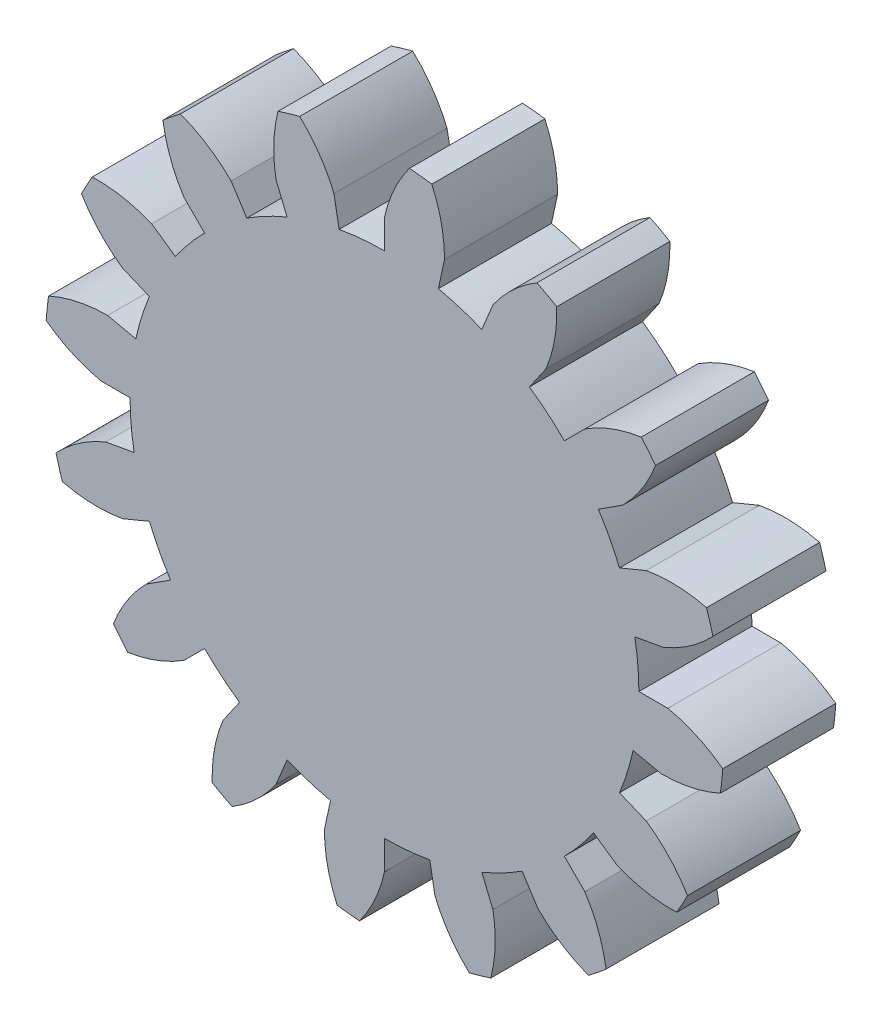
SolidWorks part; units mm, degrees
ref_plane "Plan de face" through (0, 0, 0) normal (0, 0, 1) x (1, 0, 0)
ref_plane "Plan de dessus" through (0, 0, 0) normal (0, 1, 0) x (1, 0, 0)
ref_plane "Plan de droite" through (0, 0, 0) normal (1, 0, 0) x (0, 0, -1)
sketch "Esquisse1" plane through (0, 0, 0) normal (0, 0, 1) x (1, 0, 0)
  circle A0 centre (0, 0) radius 8
  circle A1 centre (0, 0) radius 9
  circle A2 centre (0, 0) radius 6.75
  circle A3 centre (0, 0) radius 7
  circle A4 centre (0, 0) radius 7.5175
  dimension "Pitch Circle" = 16
  dimension "Addendum Circle" = 18
  dimension "Root Circle" = 13.5
  dimension "Clearence Circle" = 14
  dimension "Base Circle" = 15.0351
sketch "Involute" plane through (0, 0, 0) normal (0, 0, 1) x (1, 0, 0)
  line L0 (0, 0) -> (0, 7.5175)
  line L1 (0, 0) -> (3.7588, 6.5104) construction
  line L2 (0, 0) -> (6.5104, 3.7588) construction
  line L3 (0, 0) -> (7.5175, 0) construction
  line L4 (7.5175, 0) -> (7.5175, 11.8085) construction
  line L5 (6.5104, 3.7588) -> (2.5742, 10.5764) construction
  line L6 (3.7588, 6.5104) -> (0.3499, 8.4785) construction
  line L7 (0, 0) -> (1.5607, 7.8463) construction
  line L8 (3.0615, 7.391) -> (0, 0)
  line L9 (0.8527, 7.9544) -> (0, 0) construction
  circle A0 centre (0, 0) radius 7.5175 construction
  circle A1 centre (0, 0) radius 8 construction
  arc A2 (1.5607, 7.8463) -> (0.1378, 7.9988) centre (0, 0) ccw
  spline S0 degree 3 poles (0, 7.5175) (0.6613, 10.5961) (4.9807, 11.8125) (7.5175, 11.8085) knots 0 0 0 0 1 1 1 1
  spline S1 degree 3 poles (1.5934, 7.3467) (1.5997, 10.4955) (-2.3638, 12.5998) (-4.8438, 13.1336) knots 0 0 0 0 1 1 1 1
  dimension "Involute Control" = 90
  dimension "Base Circle Quarter Circumference" = 11.8085
  dimension "D1" = 7.8724
  dimension "D2" = 3.9362
  dimension "Circular Pitch" = 22.5
  dimension "Involute Array" = 4
sketch "Esquisse4" plane through (0, 0, 0) normal (0, 0, 1) x (1, 0, 0)
  line L0 (0, 0) -> (0, 7.5175) construction
  line L1 (0, 7.5175) -> (0, 6.75)
  line L2 (1.5934, 7.3467) -> (1.4307, 6.5966)
  arc A0 (0.6611, 8.9757) -> (1.2564, 8.9119) centre (0, 0) cw
  circle A1 centre (0, 0) radius 9 construction
  arc A2 (0, 6.75) -> (1.4307, 6.5966) centre (0, 0) cw
  circle A3 centre (0, 0) radius 6.75 construction
  arc A4 (0, 7.5175) -> (0.6611, 8.9757) centre (3.704, 6.7172) cw
  arc A5 (1.2564, 8.9119) -> (1.5934, 7.3467) centre (-2.1961, 7.3497) cw
  spline S0 degree 3 poles (0, 7.5175) (0.6613, 10.5961) (4.9807, 11.8125) (7.5175, 11.8085) knots 0 0 0 0 1 1 1 1 construction
  spline S1 degree 3 poles (1.5934, 7.3467) (1.5997, 10.4955) (-2.3638, 12.5998) (-4.8438, 13.1336) knots 0 0 0 0 1 1 1 1 construction
extrude "Boss.-Extru.1" add sketch "Esquisse4" along normal blind 3
ref_axis "Axe1" through (0, 0, 0) along (0, 0, 1)
pattern_circular "Répétition circulaire2" count 16 over 360 about axis through (0, 0, 0) along (0, 0, 1) of bodies 101
sketch "Esquisse5" plane through (0, 0, 0) normal (0, 0, 1) x (1, 0, 0)
  circle A0 centre (0, 0) radius 6.75 construction
  circle A1 centre (0, 0) radius 6.75
extrude "Boss.-Extru.2" add sketch "Esquisse5" along normal up to surface (3 mm away) up to face at (-4.8605, 6.0277, 3)
equation "\"Module\" = 1"
equation "\"Nb de dents\" = 16"
equation "\"Pressure Angle\"= 20"
equation "\"Pitch Circle@Esquisse1\"= \"Module\" * \"Nb de dents\""
equation "\"Addendum Circle@Esquisse1\"= \"Pitch Circle@Esquisse1\" + ( \"Module\" * 2 )"
equation "\"Clearence Circle@Esquisse1\"= \"Pitch Circle@Esquisse1\" - ( \"Module\" * 2 )"
equation "\"Root Circle@Esquisse1\"= \"Pitch Circle@Esquisse1\" - ( ( \"Module\" * 1.25 ) * 2 )"
equation "\"Base Circle@Esquisse1\"= \"Pitch Circle@Esquisse1\" * cos ( \"Pressure Angle\" )"
equation "\"Base Circle Quarter Circumference@Involute\" = \"Base Circle@Esquisse1\" * pI / 4"
equation "\"D1@Involute\"=\"Base Circle Quarter Circumference@Involute\"/3*2"
equation "\"D2@Involute\"=\"Base Circle Quarter Circumference@Involute\"/3"
equation "\"Circular Pitch@Involute\"=360/\"Nb de dents\""
equation "\"D1@Répétition circulaire2\"= \"Nb de dents\""
